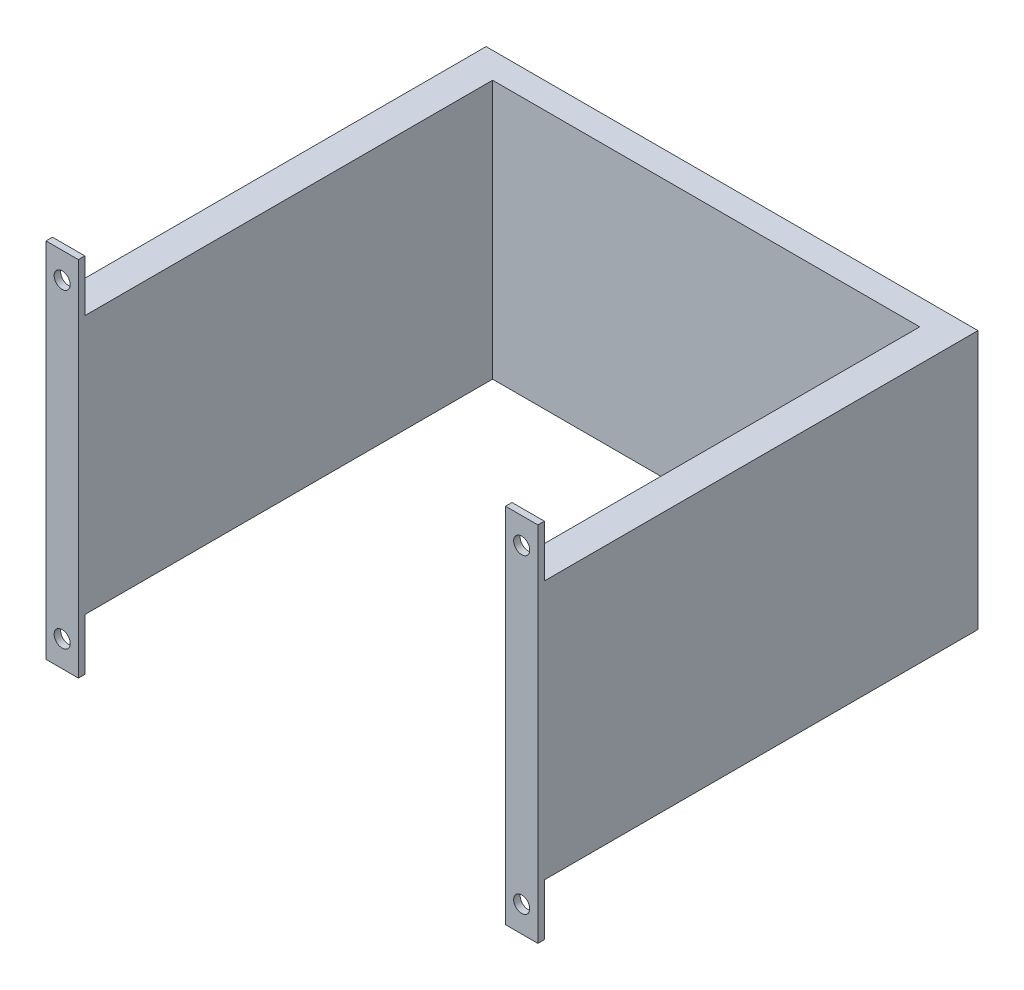
SolidWorks part; units mm, degrees
material "1060 Alloy"
ref_plane "Front Plane" through (0, 0, 0) normal (0, 0, 1) x (1, 0, 0)
ref_plane "Top Plane" through (0, 0, 0) normal (0, 1, 0) x (1, 0, 0)
ref_plane "Right Plane" through (0, 0, 0) normal (1, 0, 0) x (0, 0, -1)
sketch "Sketch1" plane through (0, 0, 0) normal (0, 0, 1) x (1, 0, 0)
  line L1 (120.65, -63.5) -> (-120.65, -63.5)
  line L2 (120.65, -63.5) -> (120.65, 63.5)
  line L3 (120.65, 63.5) -> (-120.65, 63.5)
  line L4 (-120.65, -63.5) -> (-120.65, 63.5)
  line L5 (120.65, -63.5) -> (-120.65, 63.5) construction
  line L6 (120.65, 63.5) -> (-120.65, -63.5) construction
  point P0 (0, 0)
  dimension "D1" = 127
  dimension "D2" = 241.3
extrude "Boss-Extrude1" add sketch "Sketch1" along normal blind 215.9
sketch "Sketch5" plane through (0, 0, 215.9) normal (0, 0, 1) x (1, 0, 0)
  line L1 (104.775, -63.5) -> (-104.775, -63.5)
  line L2 (104.775, -63.5) -> (104.775, 63.5)
  line L3 (104.775, 63.5) -> (-104.775, 63.5)
  line L4 (-104.775, -63.5) -> (-104.775, 63.5)
  line L5 (104.775, -63.5) -> (-104.775, 63.5) construction
  line L6 (104.775, 63.5) -> (-104.775, -63.5) construction
  point P0 (0, 0)
  dimension "D1" = 127
  dimension "D2" = 209.55
extrude "Cut-Extrude1" cut sketch "Sketch5" against normal blind 203.2
sketch "Sketch6" plane through (0, 0, 215.9) normal (0, 0, 1) x (1, 0, 0)
  line L1 (104.775, 88.9) -> (120.65, 88.9)
  line L2 (104.775, 88.9) -> (104.775, 63.5)
  line L3 (104.775, 63.5) -> (120.65, 63.5)
  line L4 (120.65, 88.9) -> (120.65, 63.5)
  line L5 (104.775, 88.9) -> (120.65, 63.5) construction
  line L6 (104.775, 63.5) -> (120.65, 88.9) construction
  line L8 (120.65, 63.5) -> (104.775, 63.5) construction
  line L9 (120.65, -63.5) -> (120.65, 63.5) construction
  line L11 (0, -83.82) -> (0, 83.82) construction
  line L12 (-104.775, 63.5) -> (-120.65, 63.5)
  line L13 (-120.65, 88.9) -> (-120.65, 63.5)
  line L14 (-104.775, 88.9) -> (-120.65, 88.9)
  line L15 (-104.775, 88.9) -> (-104.775, 63.5)
  line L16 (118.745, 0) -> (-118.745, 0) construction
  line L17 (104.775, -63.5) -> (120.65, -63.5)
  line L18 (120.65, -88.9) -> (120.65, -63.5)
  line L19 (104.775, -88.9) -> (120.65, -88.9)
  line L20 (104.775, -88.9) -> (104.775, -63.5)
  line L21 (-104.775, -88.9) -> (-104.775, -63.5)
  line L22 (-104.775, -88.9) -> (-120.65, -88.9)
  line L23 (-120.65, -88.9) -> (-120.65, -63.5)
  line L24 (-104.775, -63.5) -> (-120.65, -63.5)
  point P0 (112.7125, 76.2)
  dimension "D1" = 15.875
  dimension "D4" = 25.4
extrude "Boss-Extrude2" add sketch "Sketch6" against normal blind 3.175
sketch "Sketch7" plane through (0, 0, 212.725) normal (0, 0, -1) x (-1, 0, 0)
  line L0 (112.7125, 88.9) -> (112.7125, 63.5) construction
  line L1 (104.775, 88.9) -> (120.65, 88.9) construction
  line L2 (120.65, 63.5) -> (104.775, 63.5) construction
  line L3 (104.775, 76.2) -> (120.65, 76.2) construction
  line L4 (104.775, 63.5) -> (104.775, 88.9) construction
  line L5 (120.65, 88.9) -> (120.65, 63.5) construction
  line L6 (0, 97.79) -> (0, -97.79) construction
  line L7 (118.745, 0) -> (-118.745, 0) construction
  circle A0 centre (112.7125, 76.2) radius 3.937
  circle A1 centre (-112.7125, 76.2) radius 3.937
  circle A2 centre (112.7125, -76.2) radius 3.937
  circle A3 centre (-112.7125, -76.2) radius 3.937
  dimension "D1" = 7.874
extrude "Cut-Extrude2" cut sketch "Sketch7" against normal through all
equation "\"Height\"= 5"
equation "\"D1@Sketch1\"=\"Height\""
equation "\"D1@Sketch5\"=\"Height\""
